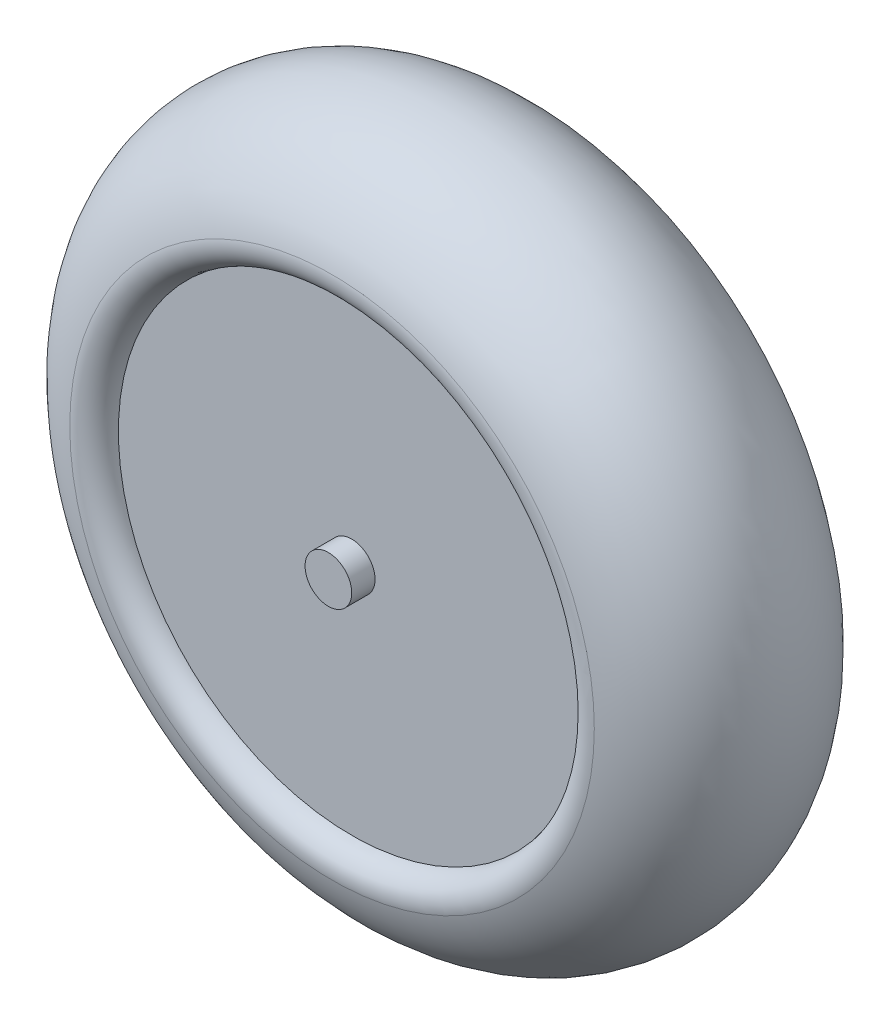
SolidWorks part; units mm, degrees
ref_plane "Front Plane" through (0, 0, 0) normal (0, 0, 1) x (1, 0, 0)
ref_plane "Top Plane" through (0, 0, 0) normal (0, 1, 0) x (1, 0, 0)
ref_plane "Right Plane" through (0, 0, 0) normal (1, 0, 0) x (0, 0, -1)
sketch "Sketch1" plane through (0, 0, 0) normal (1, 0, 0) x (0, 0, -1)
  line L1 (-12.7, 25.4) -> (12.7, 25.4)
  line L2 (0, 0) -> (42.3452, 0) construction
  arc A0 (12.7, 25.4) -> (-12.7, 25.4) centre (0, 25.4) ccw
revolve "Revolve1" add sketch "Sketch1" angle 360 about L2
sketch "Sketch4" plane through (0, 0, 0) normal (0, 0, 1) x (1, 0, 0)
  circle A0 centre (0, 0) radius 25.4 construction
  circle A1 centre (0, 0) radius 25.4
extrude "Boss-Extrude1" add sketch "Sketch4" along normal blind 10.16 and the other way blind 10.16
sketch "Sketch5" plane through (0, 0, 10.16) normal (0, 0, 1) x (1, 0, 0)
  circle A0 centre (0, 0) radius 2.54
extrude "Boss-Extrude2" add sketch "Sketch5" along normal blind 2.54
mirror "Mirror1" about plane through (0, 0, 0) normal (0, 0, 1) of "Boss-Extrude2"
fillet "Fillet1" radius 2.54 2 edges at (25.4, 0, 12.7) (25.4, 0, -12.7)
